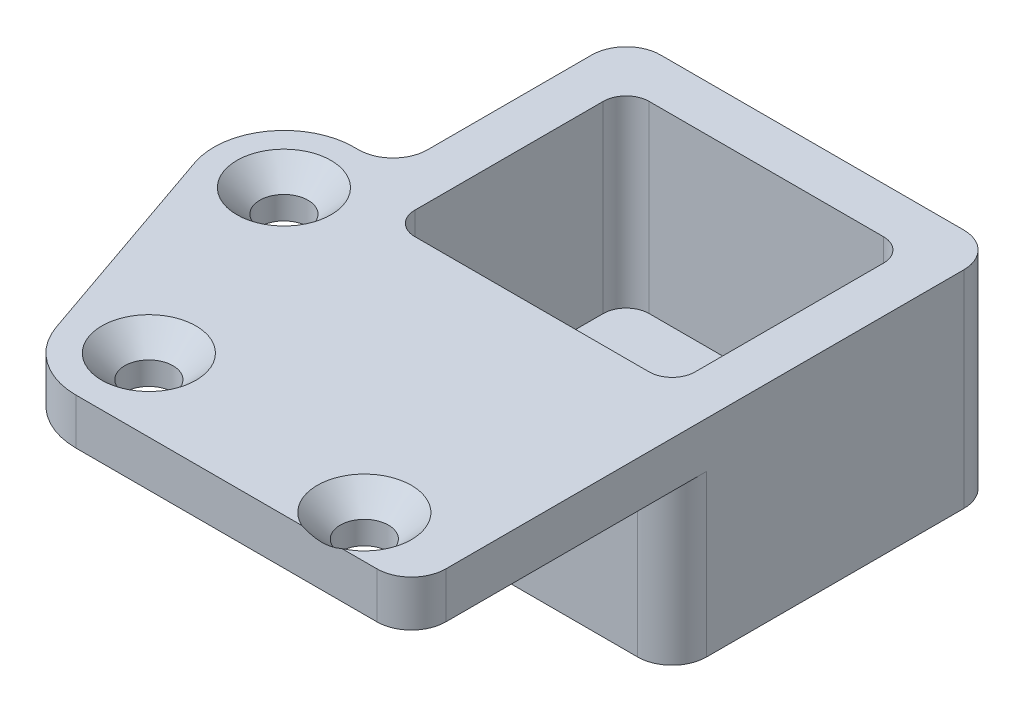
SolidWorks part; units mm, degrees
ref_plane "Front Plane" through (0, 0, 0) normal (0, 0, 1) x (1, 0, 0)
ref_plane "Top Plane" through (0, 0, 0) normal (0, 1, 0) x (1, 0, 0)
ref_plane "Right Plane" through (0, 0, 0) normal (1, 0, 0) x (0, 0, -1)
ref_axis "X-Axis" through (-88.4377, 0, 0) along (1, 0, 0)
ref_axis "Y-Axis" through (0, 0, -69.2525) along (0, 0, 1)
ref_axis "Z-Axis" through (0, -52.5493, 0) along (0, 1, 0)
sketch "Sketch1" plane through (0, 0, 0) normal (0, 1, 0) x (1, 0, 0)
  line L5 (-16.8827, -0.9964) -> (-13.6961, -10.2156)
  line L6 (-12.3, 13.2) -> (3.9, 13.2)
  line L7 (-12.3, 13.2) -> (-12.3, 3.05)
  line L9 (3.9, 13.2) -> (3.9, -1)
  line L11 (-14, 3.05) -> (-12.3, 3.05)
  line L12 (3.9, -12.35) -> (3.9, -1)
  line L14 (-12.3, 13.2) -> (3.9, -1) construction
  line L15 (-10.7, -12.35) -> (3.9, -12.35)
  line L16 (-10.3, 11.2) -> (-12.3, 11.2) construction
  line L17 (-10.3, 1) -> (1.9, 1)
  line L18 (-10.3, 1) -> (-10.3, 11.2)
  line L19 (-10.3, 11.2) -> (1.9, 11.2)
  line L20 (1.9, 1) -> (1.9, 11.2)
  line L21 (-10.3, 1) -> (1.9, 11.2) construction
  line L22 (-10.3, 11.2) -> (1.9, 1) construction
  line L23 (-10.3, 11.2) -> (-10.3, 13.2) construction
  line L24 (-14, 0) -> (0, 0) construction
  line L25 (0, 0) -> (0, -10.5) construction
  circle A0 centre (-14, 0) radius 1.05
  circle A2 centre (0, -10.5) radius 1.05
  circle A3 centre (-10.7, -9.18) radius 1.05
  arc A4 (-14, 3.05) -> (-16.8827, -0.9964) centre (-14, 0) ccw
  circle A7 centre (-14, 0) radius 3.05 construction
  arc A8 (-13.6961, -10.2156) -> (-10.7, -12.35) centre (-10.7, -9.18) ccw
  point P10 (-4.2, 6.1)
  point P14 (-4.2, 6.1)
  point P17 (0, 0)
  point P28 (0, 0)
  dimension "D5" = 2.1
  dimension "D9" = 9.8
  dimension "D1" = 14
  dimension "D2" = 10.5
  dimension "D3" = 10.7
  dimension "D4" = 1.32
  dimension "D6" = 2
  dimension "D7" = 6.1
  dimension "D11" = 1.85
  dimension "D13" = 12.2
  dimension "D14" = 10.2
  dimension "D8" = 2
extrude "Boss-Extrude1" add sketch "Sketch1" along normal blind 2
sketch "Sketch2" plane through (0, 0, 0) normal (0, -1, 0) x (1, 0, 0)
  line L10 (-10.3, -11.2) -> (-10.3, -13.2) construction
  line L11 (-10.3, -1) -> (-10.3, 1) construction
  line L12 (3.9, 12.35) -> (3.9, -13.2) construction
  line L13 (-12.3, -13.2) -> (3.9, -13.2)
  line L14 (-12.3, -13.2) -> (-12.3, 1)
  line L15 (-12.3, 1) -> (3.9, 1)
  line L16 (3.9, -13.2) -> (3.9, 1)
  line L17 (-12.3, -13.2) -> (3.9, 1) construction
  line L18 (-12.3, 1) -> (3.9, -13.2) construction
  line L19 (3.9, -13.2) -> (-12.3, -13.2) construction
  line L21 (-12.3, -13.2) -> (-12.3, -3.05) construction
  line L25 (-10.3, -11.2) -> (1.9, -11.2)
  line L26 (1.9, -11.2) -> (1.9, -1)
  line L27 (1.9, -1) -> (-10.3, -1)
  line L28 (-10.3, -1) -> (-10.3, -11.2)
  line L29 (-10.3, -11.2) -> (1.9, -11.2)
  line L30 (1.9, -11.2) -> (1.9, -1)
  line L31 (1.9, -1) -> (-10.3, -1)
  line L32 (-10.3, -1) -> (-10.3, -11.2)
  point P0 (-3.6903, -5.5)
  point P6 (-4.2, -6.1)
  dimension "D1" = 0
extrude "Boss-Extrude2" add sketch "Sketch2" along normal blind 7
sketch "Sketch4" plane through (0, -7, 0) normal (0, -1, 0) x (1, 0, 0)
  line L0 (-12.3, -13.2) -> (3.9, 1) construction
  line L1 (-12.3, 1) -> (3.9, 1)
  line L2 (-12.3, 1) -> (-12.3, -13.2)
  line L3 (-12.3, -13.2) -> (3.9, -13.2)
  line L4 (3.9, 1) -> (3.9, -13.2)
  circle A0 centre (-4.2, -6.1) radius 2
  dimension "D1" = 4
extrude "Boss-Extrude3" add sketch "Sketch4" against normal blind 1
fillet "Fillet1" radius 1.5 6 edges at (-12.3, -2.5, -13.2) (3.9, -2.5, -13.2) (3.9, 1, 12.35) (-12.3, 1, -3.05) (-12.3, -3.5, 1) (3.9, -3.5, 1)
sketch "Sketch5" plane through (0, -7, 0) normal (0, -1, 0) x (1, 0, 0)
  line L0 (-12.3, -0.5) -> (-12.3, -4.55) construction
  line L1 (-12.3, -2.3758) -> (-12.3, 1)
  line L2 (-12.3, 1) -> (-9.8404, 1)
  line L3 (2.4, 1) -> (-10.8, 1) construction
  line L4 (-12.3, -0.5) -> (-12.3, -11.7) construction
  line L5 (2.4, 1) -> (-10.8, 1) construction
  line L6 (-12.3, -2.3758) -> (-9.8404, 1)
  line L7 (-12.3, -0.5) -> (-12.3, -4.55) construction
  line L14 (2.4, 1) -> (-10.8, 1)
  line L15 (-12.3, -0.5) -> (-12.3, -11.7)
  line L16 (-10.8, -13.2) -> (2.4, -13.2)
  line L17 (3.9, -11.7) -> (3.9, -0.5)
  line L18 (2.4, 1) -> (-10.8, 1) construction
  line L19 (-12.3, -0.5) -> (-12.3, -11.7) construction
  line L20 (-10.8, -13.2) -> (2.4, -13.2) construction
  line L21 (3.9, -11.7) -> (3.9, -0.5) construction
  arc A8 (-10.8, 1) -> (-12.3, -0.5) centre (-10.8, -0.5) ccw
  arc A9 (-12.3, -11.7) -> (-10.8, -13.2) centre (-10.8, -11.7) ccw
  arc A10 (2.4, -13.2) -> (3.9, -11.7) centre (2.4, -11.7) ccw
  arc A11 (3.9, -0.5) -> (2.4, 1) centre (2.4, -0.5) ccw
  arc A12 (-10.8, 1) -> (-12.3, -0.5) centre (-10.8, -0.5) ccw construction
  arc A13 (-12.3, -11.7) -> (-10.8, -13.2) centre (-10.8, -11.7) ccw construction
  arc A14 (2.4, -13.2) -> (3.9, -11.7) centre (2.4, -11.7) ccw construction
  arc A15 (3.9, -0.5) -> (2.4, 1) centre (2.4, -0.5) ccw construction
  dimension "D1" = 0
extrude "Cut-Extrude1" cut sketch "Sketch5" against normal up to surface (7 mm away) up to face at (-14, 0, 1.05)
fillet "Fillet2" radius 2 2 edges at (-9.8404, -3.5, 1) (-12.3, -3.5, -2.3758)
fillet "Fillet3" radius 1 4 edges at (-10.3, -2, -1) (1.9, -2, -1) (1.9, -2, -11.2) (-10.3, -2, -11.2)
chamfer "Chamfer2" distance 1 angle 45 3 edges at (0, 2, 11.55) (-10.7, 2, 10.23) (-14, 2, 1.05)
sketch "Sketch6" plane through (0, -7, 0) normal (0, -1, 0) x (1, 0, 0)
  line L1 (-9.2, -10.1) -> (0.8, -10.1) construction
  line L2 (-9.2, -10.1) -> (-9.2, -2.1) construction
  line L3 (-9.2, -2.1) -> (0.8, -2.1) construction
  line L4 (0.8, -10.1) -> (0.8, -2.1) construction
  line L5 (-9.2, -10.1) -> (0.8, -2.1) construction
  line L6 (-9.2, -2.1) -> (0.8, -10.1) construction
  circle A0 centre (-9.2, -6.1) radius 0.8
  circle A1 centre (0.8, -6.1) radius 0.8
  point P0 (-4.2, -6.1)
  dimension "D1" = 1.6
  dimension "D2" = 8
  dimension "D3" = 10
extrude "Cut-Extrude2" cut sketch "Sketch6" against normal up to surface (1 mm away) up to face at (-4.2, -6, -6.1)
chamfer "Chamfer3" distance 0.8 angle 45 2 edges at (-9.2, -7, -6.9) (0.8, -7, -6.9)
